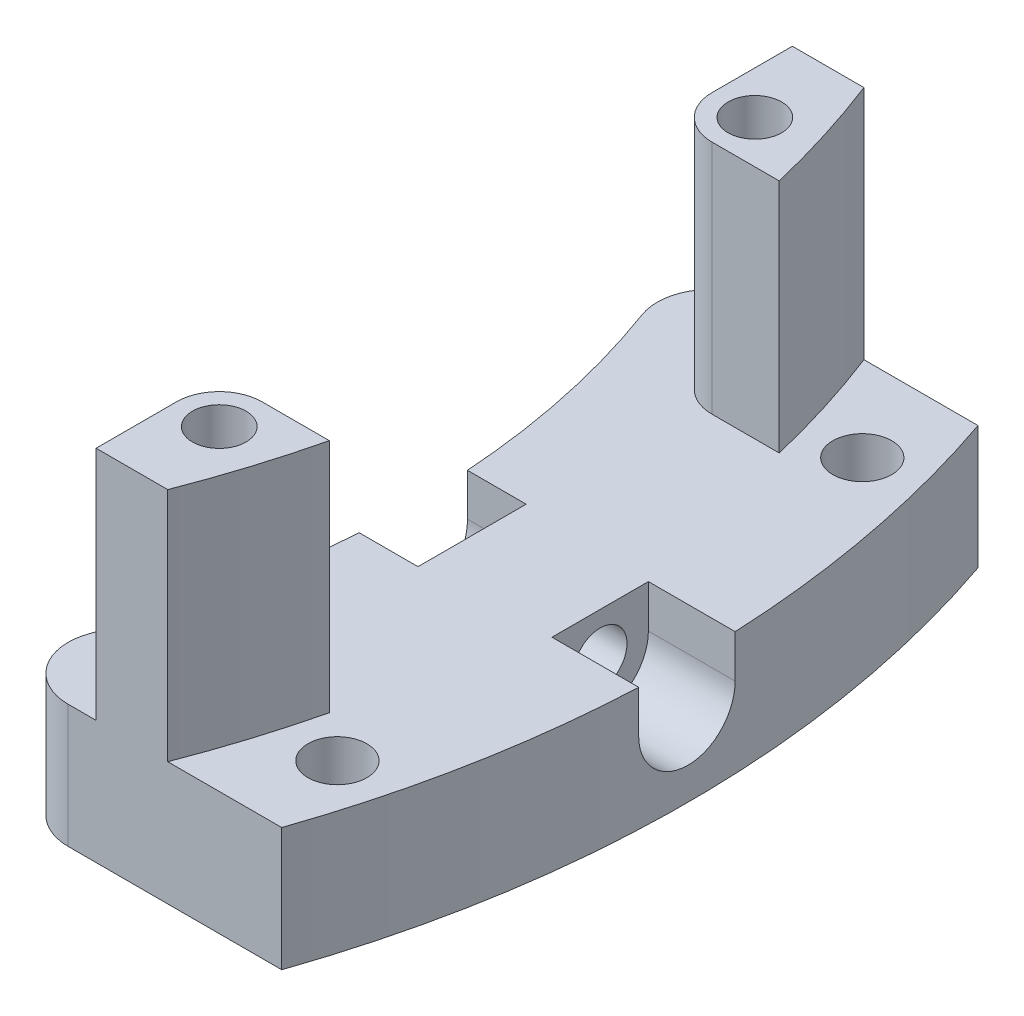
SolidWorks part; units mm, degrees
ref_plane "Front Plane" through (0, 0, 0) normal (0, 0, 1) x (1, 0, 0)
ref_plane "Top Plane" through (0, 0, 0) normal (0, 1, 0) x (1, 0, 0)
ref_plane "Right Plane" through (0, 0, 0) normal (1, 0, 0) x (0, 0, -1)
sketch "Sketch1" plane through (0, 0, 0) normal (0, 1, 0) x (1, 0, 0)
  line L0 (67.0714, -32.5) -> (94.5714, -32.5)
  line L1 (67.0714, 32.5) -> (94.5714, 32.5)
  line L2 (0, -32.5) -> (67.0714, -32.5) construction
  line L3 (-6.4979, 32.5) -> (67.0714, 32.5) construction
  line L6 (0, 32.5) -> (94.5714, 32.5) construction
  arc A0 (94.5714, 32.5) -> (94.5714, -32.5) centre (0, 0) cw
  arc A1 (67.0714, 32.5) -> (67.0714, -32.5) centre (0, 0) cw
  circle A2 centre (0, 0) radius 32.5 construction
  dimension "D1" = 100
  dimension "D3" = 27.5
  dimension "D4" = 65
extrude "Boss-Extrude1" add sketch "Sketch1" along normal blind 11.5
sketch "Sketch2" plane through (0, 11.5, 0) normal (0, -1, 0) x (1, 0, 0)
  line L0 (67.0714, 32.5) -> (94.5714, 32.5) construction
  line L1 (94.5714, -32.5) -> (67.0714, -32.5) construction
  line L2 (94.5714, -32.5) -> (67.0714, -32.5) construction
  line L3 (81.2404, 21) -> (87.5157, 21)
  line L4 (77.2404, 25) -> (77.2404, 32.5)
  line L5 (67.0714, 32.5) -> (94.5714, 32.5) construction
  line L6 (77.2404, 32.5) -> (83.9271, 32.5)
  line L7 (77.2404, -25) -> (77.2404, -32.5)
  line L8 (81.2404, -21) -> (87.5157, -21)
  line L9 (83.9271, -32.5) -> (77.2404, -32.5)
  arc A0 (83.9271, 32.5) -> (83.9271, -32.5) centre (0, 0) cw construction
  arc A1 (94.5714, -32.5) -> (94.5714, 32.5) centre (0, 0) ccw construction
  arc A2 (77.2404, 25) -> (81.2404, 21) centre (81.2404, 25) ccw
  circle A3 centre (81.2404, 25) radius 5 construction
  arc A4 (81.2404, -21) -> (77.2404, -25) centre (81.2404, -25) ccw
  circle A5 centre (81.2404, -25) radius 5 construction
  arc A6 (83.9271, 32.5) -> (87.5157, 21) centre (0, 0) cw
  arc A7 (83.9271, -32.5) -> (87.5157, -21) centre (0, 0) ccw
  dimension "D1" = 10
  dimension "D2" = 10
  dimension "D4" = 8
  dimension "D5" = 7.5
  dimension "D3" = 7.5
extrude "Boss-Extrude2" add sketch "Sketch2" against normal offset from surface (22 mm away) 22
sketch "Sketch3" plane through (0, 33.5, 0) normal (0, 1, 0) x (1, 0, 0)
  circle A0 centre (81.2404, 25) radius 2.5
  circle A1 centre (81.2404, -25) radius 2.5
  dimension "D1" = 5
extrude "Cut-Extrude1" cut sketch "Sketch3" against normal blind 4
sketch "Sketch4" plane through (0, 0, 0) normal (0, -1, 0) x (1, 0, 0)
  circle A0 centre (91.7683, 24.5) radius 4.5
  circle A1 centre (91.7683, -24.5) radius 4.5
  dimension "D1" = 9
extrude "Cut-Extrude2" cut sketch "Sketch4" against normal blind 5
sketch "Sketch5" plane through (0, 5, 0) normal (0, -1, 0) x (1, 0, 0)
  circle A0 centre (91.7683, 24.5) radius 2.75
  circle A1 centre (91.7683, -24.5) radius 2.75
  dimension "D1" = 5.5
extrude "Cut-Extrude3" cut sketch "Sketch5" against normal through all
ref_plane "Plane1" through (67.0714, 0, 0) normal (-1, 0, 0) x (0, 0, 1)
sketch "Sketch6" plane through (67.0714, 0, 0) normal (-1, 0, 0) x (0, 0, 1)
  line L1 (32.5, 11.5) -> (-32.5, 11.5) construction
  circle A0 centre (0, 7.5) radius 5 construction
  circle A1 centre (0, 7.5) radius 2.5
  circle A2 centre (0, 7.5) radius 4.5 construction
  dimension "D1" = 10
  dimension "D2" = 4
  dimension "D3" = 5
  dimension "D4" = 9
extrude "Cut-Extrude4" cut sketch "Sketch6" against normal through all
ref_plane "Plane2" through (100, 0, 0) normal (1, 0, 0) x (0, 0, -1)
ref_plane "Plane3" through (83.5357, 0, 0) normal (1, 0, 0) x (0, 0, -1)
sketch "Sketch8" plane through (100, 0, 0) normal (1, 0, 0) x (0, 0, -1)
  line L0 (-4.5, 7.5) -> (-4.5, 11.5)
  line L1 (32.5, 11.5) -> (-32.5, 11.5) construction
  line L2 (4.5, 7.5) -> (4.5, 11.5)
  line L3 (4.5, 11.5) -> (-4.5, 11.5)
  arc A1 (-4.5, 7.5) -> (4.5, 7.5) centre (0, 7.5) ccw
  dimension "D1" = 9
extrude "Cut-Extrude5" cut sketch "Sketch8" against normal blind 8.2
sketch "Sketch7" plane through (0, 11.5, 0) normal (0, 1, 0) x (1, 0, 0)
  line L1 (71.8405, 5.05) -> (71.8405, -5.05) construction
  line L2 (0, 0) -> (71.8405, 0) construction
  line L3 (71.8405, 5.05) -> (96.8405, 5.05) construction
  line L4 (96.8405, 5.05) -> (96.8405, -5.05) construction
  line L5 (96.8405, -5.05) -> (71.8405, -5.05) construction
  line L7 (91.8, 4.5) -> (91.8, -4.5) construction
  line L10 (71.8405, 5.05) -> (71.8405, -5.05)
  line L11 (71.8405, -5.05) -> (79.8405, -5.05)
  line L12 (79.8405, -5.05) -> (79.8405, 5.05)
  line L13 (79.8405, 5.05) -> (71.8405, 5.05)
  line L14 (91.8405, 5.05) -> (91.8405, -5.05) construction
  line L16 (67.0714, -32.5) -> (77.2404, -32.5) construction
  line L17 (77.2404, 32.5) -> (67.0714, 32.5) construction
  arc A1 (73.101, 32.5) -> (73.101, -32.5) centre (0, 0) cw construction
  point P15 (91.8, 0)
  dimension "D3" = 8
  dimension "D5" = 80
  dimension "D1" = 10.1
  dimension "D2" = 25
  dimension "D4" = 5
extrude "Cut-Extrude6" cut sketch "Sketch7" against normal blind 9
fillet "Fillet1" radius 5.05 2 edges at (77.0999, 2.5, 5.05) (77.0999, 2.5, -5.05)
fillet "Fillet2" radius 5 2 edges at (67.0714, 5.75, 32.5) (67.0714, 5.75, -32.5)
